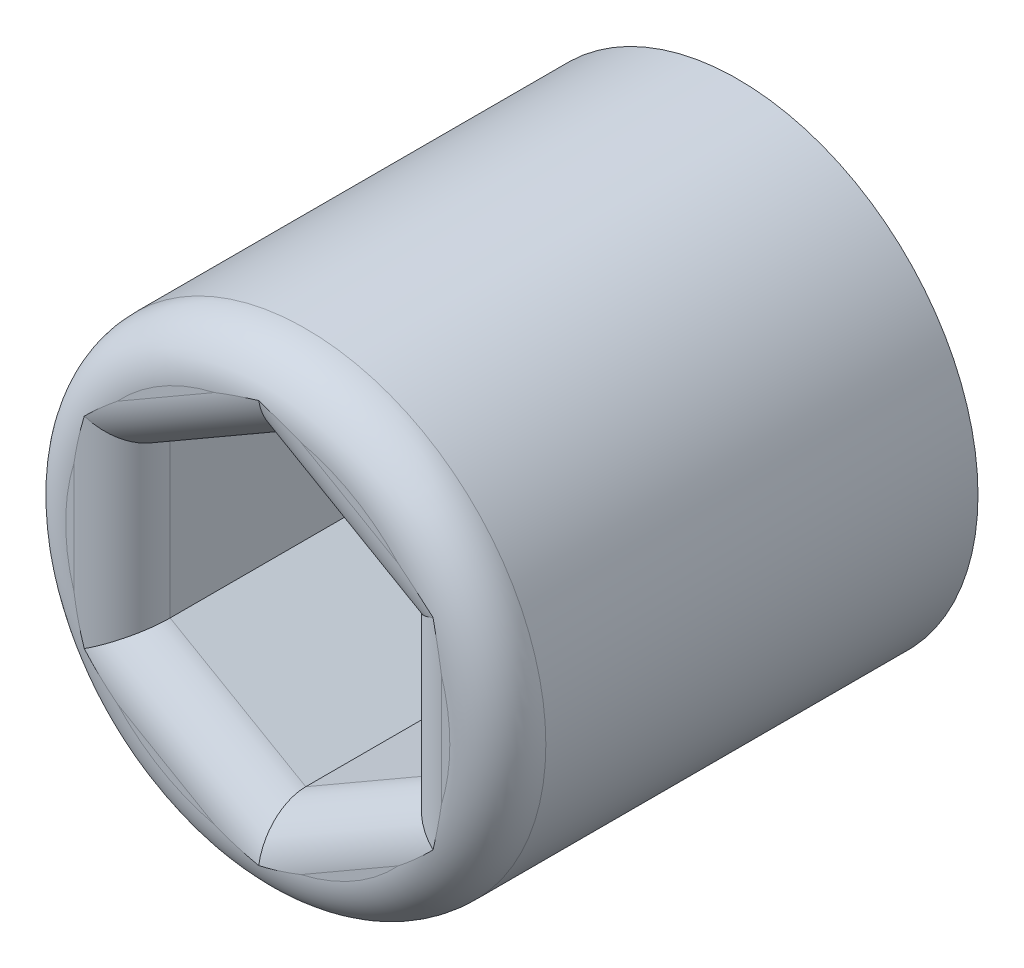
SolidWorks part; units mm, degrees
ref_plane "Спереди" through (0, 0, 0) normal (0, 0, 1) x (1, 0, 0)
ref_plane "Сверху" through (0, 0, 0) normal (0, 1, 0) x (1, 0, 0)
ref_plane "Справа" through (0, 0, 0) normal (1, 0, 0) x (0, 0, -1)
sketch "Эскиз1" plane through (0, 0, 0) normal (0, 0, 1) x (1, 0, 0)
  circle A0 centre (0, 0) radius 5
extrude "Бобышка-Вытянуть1" add sketch "Эскиз1" along normal blind 10
sketch "Эскиз2" plane through (0, 0, 10) normal (0, 0, 1) x (1, 0, 0)
  line L1 (2.825, -1.631) -> (2.825, 1.631)
  line L2 (2.825, 1.631) -> (0, 3.262)
  line L3 (0, 3.262) -> (-2.825, 1.631)
  line L4 (-2.825, 1.631) -> (-2.825, -1.631)
  line L5 (-2.825, -1.631) -> (0, -3.262)
  line L6 (0, -3.262) -> (2.825, -1.631)
  circle A0 centre (0, 0) radius 2.825 construction
  dimension "D1" = 5.65
extrude "Вырез-Вытянуть3" cut sketch "Эскиз2" against normal blind 8
sketch "Эскиз3" plane through (0, 0, 2) normal (0, 0, 1) x (1, 0, 0)
  circle A0 centre (0, 0) radius 1.8
extrude "Вырез-Вытянуть4" cut sketch "Эскиз3" against normal blind 8
fillet "Скругление3" radius 1 1 edges at (5, 0, 10)
fillet "Скругление7" radius 1 1 edges at (1.4125, 2.4465, 10)
fillet "Скругление8" radius 1 1 edges at (2.825, 0.5774, 10)
fillet "Скругление9" radius 1 1 edges at (1.9125, -2.1578, 10)
fillet "Скругление10" radius 1 1 edges at (-0.9125, -2.7352, 10)
fillet "Скругление11" radius 1 1 edges at (-0.9125, 2.7352, 10)
fillet "Скругление12" radius 1 1 edges at (-2.825, 0, 10)
